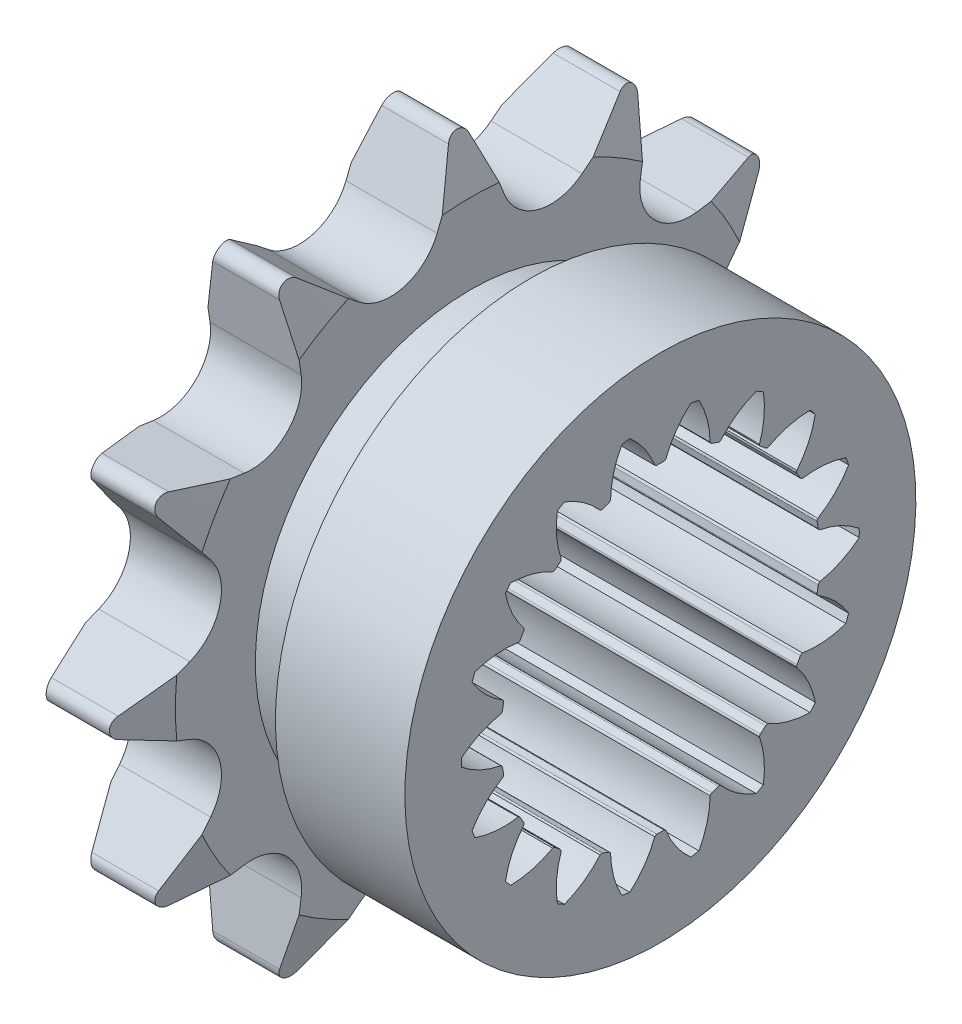
SolidWorks part; units mm, degrees
material "1144"
ref_plane "Front Plane" through (0, 0, 0) normal (0, 0, 1) x (1, 0, 0)
ref_plane "Top Plane" through (0, 0, 0) normal (0, 1, 0) x (1, 0, 0)
ref_plane "Right Plane" through (0, 0, 0) normal (1, 0, 0) x (0, 0, -1)
ref_axis "Axis1" through (-63.0158, 0, 0) along (1, 0, 0)
sketch "Sketch1" plane through (0, 0, 0) normal (0, 0, 1) x (1, 0, 0)
  line L0 (3.6068, 17.0561) -> (3.6068, 0) construction
  line L1 (22.225, 0) -> (22.225, 20.2311)
  line L3 (7.2136, 17.0561) -> (0, 17.0561)
  line L7 (0, 27.5082) -> (0, 30.0482) construction
  line L8 (0, 27.5082) -> (7.2136, 27.5082)
  line L9 (22.225, 0) -> (0, 0)
  line L10 (0, 0) -> (-84.1773, 0) construction
  line L11 (0, 17.0561) -> (0, 27.5082) construction
  line L12 (7.2136, 27.5082) -> (73.2462, 27.5082) construction
  line L13 (22.225, 0) -> (22.225, -20.2311) construction
  line L14 (3.6068, 0) -> (3.6068, -17.0561)
  line L15 (-15.4432, -17.0561) -> (22.6568, -17.0561)
  point P11 (0, 30.0482)
  dimension "D1" = 2.54
  dimension "hub_dia" = 40.4622
  dimension "width_teetth" = 7.2136
  dimension "D2" = 38.1
  dimension "length_thru" = 22.225
  dimension "OD" = 55.0164
  dimension "length_over_teeth" = 7.2136
  dimension "recess_hub_diam" = 34.1122
  dimension "hub_type" = 22.225
  dimension "projection 1" = 15.0114
  dimension "projection 2" = 0
sketch "Sketch2" plane through (0, 0, 0) normal (1, 0, 0) x (0, 0, -1)
  line L0 (0, 0) -> (0, 27.5082) construction
  line L1 (0, 0) -> (-13.7541, 23.8228) construction
  line L2 (0, 0) -> (-6.3502, 23.6991) construction
  line L3 (-0.8057, 26.9597) -> (-2.6638, 22.246)
  line L4 (-2.6638, 22.246) -> (-6.3502, 23.6991) construction
  line L5 (-0.8217, 27.4959) -> (0, 0) construction
  line L6 (-2.735, 27.3719) -> (0, 0) construction
  line L7 (-6.3502, 23.6991) -> (-2.4074, 24.0931) construction
  arc A1 (0, 27.5082) -> (-13.7541, 23.8228) centre (0, 0) ccw
  circle A2 centre (0, 0) radius 24.5351 construction
  circle A3 centre (-6.3502, 23.6991) radius 3.9624
  arc A4 (0, 27.5082) -> (-0.8057, 26.9597) centre (0, 26.6421) ccw
  dimension "pitch_diam" = 49.0703
  dimension "roller_diam" = 7.9248
  dimension "D1" = 1.712
  dimension "ang_1" = 30
  dimension "OD/2" = 27.5082
sketch "Taper Per Foot" plane through (0, 0, 0) normal (0, 0, 1) x (1, 0, 0)
  line L0 (22.225, 0) -> (22.225, 127)
  line L1 (22.225, 0) -> (22.225, 20.2311) construction
  line L2 (22.225, 127) -> (-282.575, 6.35)
  line L3 (-282.575, 6.35) -> (-282.575, 0)
  line L4 (-282.575, 0) -> (22.225, 0)
  line L5 (-282.575, 0) -> (-285.7823, 0) construction
  line L6 (-282.575, 6.35) -> (22.225, 6.35)
  line L7 (22.225, 6.35) -> (22.225, 127)
  dimension "1 Ft" = 304.8
  dimension "1 in" = 254
  dimension "Small End Diam" = 12.7
  dimension "Large End Diam" = 12.7
ref_plane "Plane1" through (7.2136, 0, 0) normal (1, 0, 0) x (0, 0, -1)
ref_plane "Plane2" through (7.2136, 0, 0) normal (1, 0, 0) x (0, 0, -1)
ref_plane "Plane3" through (0, 17.0561, 0) normal (-1, 0, 0) x (0, 0, 1)
ref_plane "Plane4" through (22.225, 0, 0) normal (1, 0, 0) x (0, 0, -1)
ref_plane "Plane5" through (3.6068, 0, 0) normal (1, 0, 0) x (0, 0, -1)
sketch "Sketch13" plane through (0, 0, 0) normal (0, 0, 1) x (1, 0, 0)
  line L0 (22.225, 0) -> (22.225, 20.2311) construction
  line L1 (0, 0) -> (22.225, 0)
  line L2 (0, 0) -> (0, 27.5082)
  line L3 (0, 27.5082) -> (22.225, 27.5082)
  line L4 (22.225, 0) -> (22.225, 27.5082)
revolve "Revolve1" add sketch "Sketch13" angle 360 about L10
sketch "Sketch6" plane through (0, -16.51, 0) normal (1, 0, 0) x (0, 0, -1)
  line L0 (-0.8057, 43.4697) -> (-2.6638, 38.756) construction
  line L1 (-0.8057, 43.4697) -> (-2.6638, 38.756)
  line L2 (-6.3502, 40.2091) -> (0, 16.51) construction
  line L3 (-12.7821, 40.2607) -> (-8.8161, 37.1075)
  arc A0 (0, 44.0182) -> (-0.8057, 43.4697) centre (0, 43.1521) ccw construction
  arc A1 (0, 44.0182) -> (-0.8057, 43.4697) centre (0, 43.1521) ccw
  arc A2 (-13.7541, 40.3328) -> (-12.7821, 40.2607) centre (-13.3211, 39.5828) cw
  arc A3 (-2.6638, 38.756) -> (-8.8161, 37.1075) centre (-6.3502, 40.2091) cw
  arc A4 (0, 44.0182) -> (-13.7541, 40.3328) centre (0, 16.51) ccw
extrude "Cut-Extrude1" cut sketch "Sketch6" along normal up to vertex (7.0866 mm away) up to point (7.2136, 17.0561, 0)
pattern_circular "CirPattern1" count 12 over 360 about axis through (-63.0158, 0, 0) along (1, 0, 0) of "Cut-Extrude1"
sketch "Sketch15" plane through (0, 0, 0) normal (0, 0, 1) x (1, 0, 0)
  line L1 (134.2136, 20.2311) -> (7.2136, 20.2311)
  line L2 (134.2136, 20.2311) -> (134.2136, 42.7482)
  line L3 (134.2136, 42.7482) -> (7.2136, 42.7482)
  line L4 (7.2136, 20.2311) -> (7.2136, 42.7482)
  line L5 (3.6068, 216.4797) -> (3.6068, 17.0561) construction
  line L6 (-127, 20.2311) -> (0, 20.2311)
  line L7 (0, 20.2311) -> (0, 42.7482)
  line L8 (-127, 42.7482) -> (0, 42.7482)
  line L9 (-127, 20.2311) -> (-127, 42.7482)
  dimension "D1" = 12.7
  dimension "D2" = 127
revolve "hub Cut-Revolve3" cut sketch "Sketch15" angle 360 about L10
sketch "Sketch4" plane through (0, 0, 0) normal (0, 0, 1) x (1, 0, 0)
  line L0 (0, 27.5082) -> (1.1045, 27.5082)
  line L2 (1.1045, 27.5082) -> (0, 23.3861)
  line L4 (0, 23.3861) -> (0, 27.5082)
  line L5 (3.6068, 27.5082) -> (3.6068, 44.9612) construction
  line L6 (7.2136, 27.5082) -> (6.1091, 27.5082)
  line L7 (7.2136, 23.3861) -> (7.2136, 27.5082)
  line L8 (6.1091, 27.5082) -> (7.2136, 23.3861)
  line L9 (0, 0) -> (-52.1231, 0) construction
  line L10 (0, 0) -> (-84.1773, 0) construction
  line L17 (0, 27.5082) -> (7.2136, 27.5082) construction
  dimension "D1" = 15
  dimension "D2" = 4.1221
revolve "Teeth Chamfer" cut sketch "Sketch4" angle 360 about L9
sketch "Sketch16" plane through (0, 0, 0) normal (0, 0, 1) x (1, 0, 0)
  line L1 (7.2136, 20.2311) -> (11.9761, 20.2311)
  line L2 (7.2136, 20.2311) -> (7.2136, 17.0561)
  line L3 (7.2136, 17.0561) -> (11.9761, 17.0561)
  line L4 (11.9761, 20.2311) -> (11.9761, 17.0561)
  line L5 (11.9761, 20.2311) -> (22.225, 20.2311) construction
  dimension "recess_width" = 4.7625
  dimension "recess_height" = 3.175
revolve "Recess" cut sketch "Sketch16" angle 360 about L10
sketch "Sketch32" plane through (22.225, 0, 0) normal (1, 0, 0) x (0, 0, -1)
  circle A1 centre (0, 0) radius 20.2311
  circle A2 centre (0, 0) radius 20.2311
  dimension "D1" = 0
extrude "Collar Reduction" [suppressed] cut sketch "Sketch32" against normal offset from surface (2.455 mm away) 19.77
ref_plane "Sprocket Teeth Center" through (3.6068, 0, 0) normal (-1, 0, 0) x (0, 0, 1)
sketch "Sketch35" plane through (3.6068, 0, 0) normal (1, 0, 0) x (0, 0, -1)
  circle A0 centre (0, 0) radius 24.5351 construction
  circle A1 centre (0, 0) radius 24.5351 construction
sketch "Sketch36" plane through (0, 0, 0) normal (-1, 0, 0) x (0, 0, 1)
  arc A34 (-7.5926, 13.7968) -> (-4.773, 11.8201) centre (-10.1337, 7.1728) cw
  arc A35 (-4.773, 11.8201) -> (-4.5847, 11.7902) centre (-4.6432, 12.0297) ccw
  arc A36 (-0.6644, 3.068) -> (-0.7894, 2.924) centre (-0.8986, 3.1451) cw
  arc A37 (-4.5847, 11.7902) -> (-4.0582, 11.9816) centre (0, 0) cw
  arc A38 (-8.1521, 13.4738) -> (-7.5639, 13.8125) centre (0, 0) cw
  arc A39 (-8.3407, 9.5111) -> (-7.9114, 9.8711) centre (0, 0) cw
  arc A40 (-7.85, 10.0436) -> (-7.9183, 9.8655) centre (-8.0965, 10.0359) cw
  arc A41 (-8.1521, 13.4738) -> (-7.85, 10.0436) centre (-1.145, 12.3625) ccw
  arc A42 (-2.4159, 15.5616) -> (-0.4424, 12.7398) centre (-7.0693, 10.2062) cw
  arc A43 (-0.4424, 12.7398) -> (-0.2757, 12.6472) centre (-0.2487, 12.8923) ccw
  arc A44 (-0.2757, 12.6472) -> (0.2845, 12.647) centre (0, 0) cw
  arc A45 (-3.0522, 15.4494) -> (-2.3836, 15.5666) centre (0, 0) cw
  arc A46 (-4.5847, 11.7902) -> (-4.0582, 11.9816) centre (0, 0) cw
  arc A47 (-3.9415, 12.1228) -> (-4.0666, 11.9788) centre (-4.1757, 12.1999) cw
  arc A48 (-3.0522, 15.4494) -> (-3.9415, 12.1228) centre (3.1523, 12.0085) ccw
  arc A49 (3.0522, 15.4494) -> (3.9415, 12.1228) centre (-3.1523, 12.0085) cw
  arc A50 (3.9415, 12.1228) -> (4.0666, 11.9788) centre (4.1757, 12.1999) ccw
  arc A51 (4.0666, 11.9788) -> (4.5929, 11.787) centre (0, 0) cw
  arc A52 (2.4159, 15.5616) -> (3.0842, 15.443) centre (0, 0) cw
  arc A53 (-0.2757, 12.6472) -> (0.2845, 12.647) centre (0, 0) cw
  arc A54 (0.4424, 12.7398) -> (0.2757, 12.6472) centre (0.2487, 12.8923) cw
  arc A55 (2.4159, 15.5616) -> (0.4424, 12.7398) centre (7.0693, 10.2062) ccw
  arc A56 (8.1521, 13.4738) -> (7.85, 10.0436) centre (1.145, 12.3625) cw
  arc A57 (7.85, 10.0436) -> (7.9183, 9.8655) centre (8.0965, 10.0359) ccw
  arc A58 (7.9183, 9.8655) -> (8.3473, 9.5053) centre (0, 0) cw
  arc A59 (7.5926, 13.7968) -> (8.18, 13.4568) centre (0, 0) cw
  arc A60 (4.0666, 11.9788) -> (4.5929, 11.787) centre (0, 0) cw
  arc A61 (4.773, 11.8201) -> (4.5847, 11.7902) centre (4.6432, 12.0297) cw
  arc A62 (7.5926, 13.7968) -> (4.773, 11.8201) centre (10.1337, 7.1728) ccw
  arc A63 (12.2688, 9.873) -> (10.8117, 6.753) centre (5.3042, 11.2253) cw
  arc A64 (10.8117, 6.753) -> (10.815, 6.5624) centre (11.0407, 6.6616) ccw
  arc A65 (10.815, 6.5624) -> (11.0949, 6.0771) centre (0, 0) cw
  arc A66 (11.8535, 10.368) -> (12.2892, 9.8476) centre (0, 0) cw
  arc A67 (7.9183, 9.8655) -> (8.3473, 9.5053) centre (0, 0) cw
  arc A68 (8.5279, 9.4748) -> (8.3407, 9.5111) centre (8.4775, 9.7162) cw
  arc A69 (11.8535, 10.368) -> (8.5279, 9.4748) centre (11.9758, 3.2743) ccw
  arc A70 (14.9057, 5.0814) -> (12.4694, 2.6479) centre (8.8236, 8.7342) cw
  arc A71 (12.4694, 2.6479) -> (12.4072, 2.4677) centre (12.6532, 2.4837) ccw
  arc A72 (12.4072, 2.4677) -> (12.5043, 1.916) centre (0, 0) cw
  arc A73 (14.6847, 5.6886) -> (14.9162, 5.0505) centre (0, 0) cw
  arc A74 (10.815, 6.5624) -> (11.0949, 6.0771) centre (0, 0) cw
  arc A75 (11.2542, 5.9867) -> (11.0907, 6.0849) centre (11.2894, 6.2307) cw
  arc A76 (14.6847, 5.6886) -> (11.2542, 5.9867) centre (12.3735, -1.0191) ccw
  arc A77 (15.7447, -0.3231) -> (12.623, -1.7765) centre (11.2787, 5.1896) cw
  arc A78 (12.623, -1.7765) -> (12.503, -1.9247) centre (12.7396, -1.9938) ccw
  arc A79 (12.503, -1.9247) -> (12.4055, -2.4763) centre (0, 0) cw
  arc A80 (15.7447, 0.3231) -> (15.744, -0.3557) centre (0, 0) cw
  arc A81 (12.4072, 2.4677) -> (12.5043, 1.916) centre (0, 0) cw
  arc A82 (12.623, 1.7765) -> (12.503, 1.9247) centre (12.7396, 1.9938) cw
  arc A83 (15.7447, 0.3231) -> (12.623, 1.7765) centre (11.2787, -5.1896) ccw
  arc A84 (14.6847, -5.6886) -> (11.2542, -5.9867) centre (12.3735, 1.0191) cw
  arc A85 (11.2542, -5.9867) -> (11.0907, -6.0849) centre (11.2894, -6.2307) ccw
  arc A86 (11.0907, -6.0849) -> (10.8104, -6.5699) centre (0, 0) cw
  arc A87 (14.9057, -5.0814) -> (14.6728, -5.719) centre (0, 0) cw
  arc A88 (12.503, -1.9247) -> (12.4055, -2.4763) centre (0, 0) cw
  arc A89 (12.4694, -2.6479) -> (12.4072, -2.4677) centre (12.6532, -2.4837) cw
  arc A90 (14.9057, -5.0814) -> (12.4694, -2.6479) centre (8.8236, -8.7342) ccw
  arc A91 (11.8535, -10.368) -> (8.5279, -9.4748) centre (11.9758, -3.2743) cw
  arc A92 (8.5279, -9.4748) -> (8.3407, -9.5111) centre (8.4775, -9.7162) ccw
  arc A93 (8.3407, -9.5111) -> (7.9114, -9.8711) centre (0, 0) cw
  arc A94 (12.2688, -9.873) -> (11.832, -10.3925) centre (0, 0) cw
  arc A95 (11.0907, -6.0849) -> (10.8104, -6.5699) centre (0, 0) cw
  arc A96 (10.8117, -6.753) -> (10.815, -6.5624) centre (11.0407, -6.6616) cw
  arc A97 (12.2688, -9.873) -> (10.8117, -6.753) centre (5.3042, -11.2253) ccw
  arc A98 (7.5926, -13.7968) -> (4.773, -11.8201) centre (10.1337, -7.1728) cw
  arc A99 (4.773, -11.8201) -> (4.5847, -11.7902) centre (4.6432, -12.0297) ccw
  arc A100 (4.5847, -11.7902) -> (4.0582, -11.9816) centre (0, 0) cw
  arc A101 (8.1521, -13.4738) -> (7.5639, -13.8125) centre (0, 0) cw
  arc A102 (8.3407, -9.5111) -> (7.9114, -9.8711) centre (0, 0) cw
  arc A103 (7.85, -10.0436) -> (7.9183, -9.8655) centre (8.0965, -10.0359) cw
  arc A104 (8.1521, -13.4738) -> (7.85, -10.0436) centre (1.145, -12.3625) ccw
  arc A105 (2.4159, -15.5616) -> (0.4424, -12.7398) centre (7.0693, -10.2062) cw
  arc A106 (0.4424, -12.7398) -> (0.2757, -12.6472) centre (0.2487, -12.8923) ccw
  arc A107 (0.2757, -12.6472) -> (-0.2845, -12.647) centre (0, 0) cw
  arc A108 (3.0522, -15.4494) -> (2.3836, -15.5666) centre (0, 0) cw
  arc A109 (4.5847, -11.7902) -> (4.0582, -11.9816) centre (0, 0) cw
  arc A110 (3.9415, -12.1228) -> (4.0666, -11.9788) centre (4.1757, -12.1999) cw
  arc A111 (3.0522, -15.4494) -> (3.9415, -12.1228) centre (-3.1523, -12.0085) ccw
  arc A112 (-3.0522, -15.4494) -> (-3.9415, -12.1228) centre (3.1523, -12.0085) cw
  arc A113 (-3.9415, -12.1228) -> (-4.0666, -11.9788) centre (-4.1757, -12.1999) ccw
  arc A114 (-4.0666, -11.9788) -> (-4.5929, -11.787) centre (0, 0) cw
  arc A115 (-2.4159, -15.5616) -> (-3.0842, -15.443) centre (0, 0) cw
  arc A116 (0.2757, -12.6472) -> (-0.2845, -12.647) centre (0, 0) cw
  arc A117 (-0.4424, -12.7398) -> (-0.2757, -12.6472) centre (-0.2487, -12.8923) cw
  arc A118 (-2.4159, -15.5616) -> (-0.4424, -12.7398) centre (-7.0693, -10.2062) ccw
  arc A119 (-8.1521, -13.4738) -> (-7.85, -10.0436) centre (-1.145, -12.3625) cw
  arc A120 (-7.85, -10.0436) -> (-7.9183, -9.8655) centre (-8.0965, -10.0359) ccw
  arc A121 (-7.9183, -9.8655) -> (-8.3473, -9.5053) centre (0, 0) cw
  arc A122 (-7.5926, -13.7968) -> (-8.18, -13.4568) centre (0, 0) cw
  arc A123 (-4.0666, -11.9788) -> (-4.5929, -11.787) centre (0, 0) cw
  arc A124 (-4.773, -11.8201) -> (-4.5847, -11.7902) centre (-4.6432, -12.0297) cw
  arc A125 (-7.5926, -13.7968) -> (-4.773, -11.8201) centre (-10.1337, -7.1728) ccw
  arc A126 (-12.2688, -9.873) -> (-10.8117, -6.753) centre (-5.3042, -11.2253) cw
  arc A127 (-10.8117, -6.753) -> (-10.815, -6.5624) centre (-11.0407, -6.6616) ccw
  arc A128 (-10.815, -6.5624) -> (-11.0949, -6.0771) centre (0, 0) cw
  arc A129 (-11.8535, -10.368) -> (-12.2892, -9.8476) centre (0, 0) cw
  arc A130 (-7.9183, -9.8655) -> (-8.3473, -9.5053) centre (0, 0) cw
  arc A131 (-8.5279, -9.4748) -> (-8.3407, -9.5111) centre (-8.4775, -9.7162) cw
  arc A132 (-11.8535, -10.368) -> (-8.5279, -9.4748) centre (-11.9758, -3.2743) ccw
  arc A133 (-14.9057, -5.0814) -> (-12.4694, -2.6479) centre (-8.8236, -8.7342) cw
  arc A134 (-12.4694, -2.6479) -> (-12.4072, -2.4677) centre (-12.6532, -2.4837) ccw
  arc A135 (-12.4072, -2.4677) -> (-12.5043, -1.916) centre (0, 0) cw
  arc A136 (-14.6847, -5.6886) -> (-14.9162, -5.0505) centre (0, 0) cw
  arc A137 (-10.815, -6.5624) -> (-11.0949, -6.0771) centre (0, 0) cw
  arc A138 (-11.2542, -5.9867) -> (-11.0907, -6.0849) centre (-11.2894, -6.2307) cw
  arc A139 (-14.6847, -5.6886) -> (-11.2542, -5.9867) centre (-12.3735, 1.0191) ccw
  arc A140 (-15.7447, 0.3231) -> (-12.623, 1.7765) centre (-11.2787, -5.1896) cw
  arc A141 (-12.623, 1.7765) -> (-12.503, 1.9247) centre (-12.7396, 1.9938) ccw
  arc A142 (-12.503, 1.9247) -> (-12.4055, 2.4763) centre (0, 0) cw
  arc A143 (-15.7447, -0.3231) -> (-15.744, 0.3557) centre (0, 0) cw
  arc A144 (-12.4072, -2.4677) -> (-12.5043, -1.916) centre (0, 0) cw
  arc A145 (-12.623, -1.7765) -> (-12.503, -1.9247) centre (-12.7396, -1.9938) cw
  arc A146 (-15.7447, -0.3231) -> (-12.623, -1.7765) centre (-11.2787, 5.1896) ccw
  arc A147 (-14.6847, 5.6886) -> (-11.2542, 5.9867) centre (-12.3735, -1.0191) cw
  arc A148 (-11.2542, 5.9867) -> (-11.0907, 6.0849) centre (-11.2894, 6.2307) ccw
  arc A149 (-11.0907, 6.0849) -> (-10.8104, 6.5699) centre (0, 0) cw
  arc A150 (-14.9057, 5.0814) -> (-14.6728, 5.719) centre (0, 0) cw
  arc A151 (-12.503, 1.9247) -> (-12.4055, 2.4763) centre (0, 0) cw
  arc A152 (-12.4694, 2.6479) -> (-12.4072, 2.4677) centre (-12.6532, 2.4837) cw
  arc A153 (-14.9057, 5.0814) -> (-12.4694, 2.6479) centre (-8.8236, 8.7342) ccw
  arc A154 (-11.8535, 10.368) -> (-8.5279, 9.4748) centre (-11.9758, 3.2743) cw
  arc A155 (-8.5279, 9.4748) -> (-8.3407, 9.5111) centre (-8.4775, 9.7162) ccw
  arc A156 (-8.3407, 9.5111) -> (-7.9114, 9.8711) centre (0, 0) cw
  arc A157 (-12.2688, 9.873) -> (-11.832, 10.3925) centre (0, 0) cw
  arc A158 (-11.0907, 6.0849) -> (-10.8104, 6.5699) centre (0, 0) cw
  arc A159 (-10.8117, 6.753) -> (-10.815, 6.5624) centre (-11.0407, 6.6616) cw
  arc A160 (-12.2688, 9.873) -> (-10.8117, 6.753) centre (-5.3042, 11.2253) ccw
  point P6 (-8.1521, 13.4738)
  point P24 (-3.1758, 15.7377)
  point P38 (2.2923, 15.8499)
  point P52 (7.469, 14.0851)
  point P66 (11.7299, 10.6563)
  point P81 (14.5611, 5.9769)
  point P95 (15.6211, 0.6114)
  point P109 (14.7821, -4.7931)
  point P123 (12.1452, -9.5847)
  point P137 (8.0286, -13.1855)
  point P151 (2.9286, -15.1611)
  point P165 (-2.5394, -15.2733)
  point P179 (-7.7161, -13.5085)
  point P193 (-11.977, -10.0797)
  point P207 (-14.8082, -5.4003)
  point P221 (-15.8682, -0.0348)
  point P235 (-15.0292, 5.3697)
  point P248 (-12.3924, 10.1613)
  point P258 (-0.1236, 0.2883)
extrude "Cut-Extrude2" cut sketch "Sketch36" against normal through all region at (0, 0, 0)
ref_axis "Axis2" through (22.225, 0, 0) along (-1, 0, 0)
